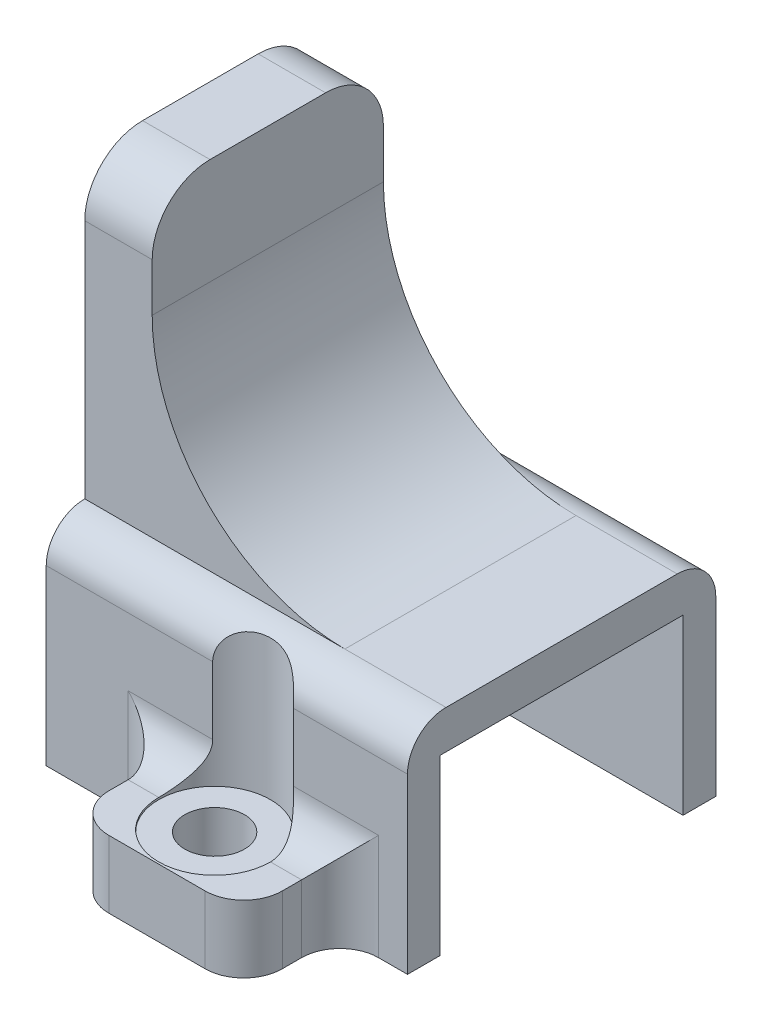
SolidWorks part; units mm, degrees
ref_plane "Alzado" through (0, 0, 0) normal (0, 0, 1) x (1, 0, 0)
ref_plane "Planta" through (0, 0, 0) normal (0, 1, 0) x (1, 0, 0)
ref_plane "Vista lateral" through (0, 0, 0) normal (1, 0, 0) x (0, 0, -1)
sketch "Croquis1" plane through (0, 0, 0) normal (0, 1, 0) x (1, 0, 0)
  line L1 (0, 0) -> (18.75, 0)
  line L2 (0, 0) -> (0, 16)
  line L3 (0, 16) -> (18.75, 16)
  line L4 (18.75, 0) -> (18.75, 16)
  dimension "D1" = 18.75
  dimension "D2" = 16
extrude "Saliente-Extruir1" add sketch "Croquis1" along normal blind 10
sketch "Croquis2" plane through (0, 0, 0) normal (0, -1, 0) x (1, 0, 0)
  line L19 (18.75, 0) -> (18.75, -16) construction
  line L20 (0, -16) -> (0, 0) construction
  line L22 (0, 0) -> (18.75, 0) construction
  line L23 (0, -1.7) -> (18.75, -1.7)
  line L24 (0, -1.7) -> (0, -14.3)
  line L25 (0, -14.3) -> (18.75, -14.3)
  line L26 (18.75, -1.7) -> (18.75, -14.3)
  line L27 (18.75, -16) -> (0, -16) construction
  point P10 (9.375, 0)
  dimension "D1" = 1.7
  dimension "D2" = 1.7
extrude "Cortar-Extruir1" cut sketch "Croquis2" against normal blind 8
sketch "Croquis3" plane through (0, 0, 0) normal (0, 0, 1) x (1, 0, 0)
  line L0 (0, 0) -> (18.75, 0) construction
  line L1 (6.25, 0) -> (15.25, 0)
  line L2 (6.25, 0) -> (6.25, 2.5)
  line L3 (6.25, 2.5) -> (15.25, 2.5)
  line L4 (15.25, 0) -> (15.25, 2.5)
  line L5 (18.75, 10) -> (18.75, 0) construction
  dimension "D1" = 2.5
  dimension "D2" = 3.5
  dimension "D3" = 9
extrude "Saliente-Extruir2" add sketch "Croquis3" along normal blind 5
sketch "Croquis4" plane through (0, 2.5, 0) normal (0, 1, 0) x (1, 0, 0)
  line L0 (18.75, 0) -> (18.75, 16) construction
  line L1 (15.25, 0) -> (6.25, 0) construction
  circle A0 centre (10.74, -2) radius 1.55
  dimension "D1" = 3.1
  dimension "D2" = 8.01
  dimension "D3" = 2
extrude "Cortar-Extruir2" cut sketch "Croquis4" against normal up to surface (2.5 mm away) up to face at (9.375, 0, -15.15)
fillet "Redondeo1" radius 2 7 edges at (9.375, 10, -16) (9.375, 10, 0) (6.25, 1.25, 5) (15.25, 1.25, 5) (10.75, 2.5, 0) (15.25, 1.25, 0) (6.25, 1.25, 0)
sketch "Croquis5" plane through (0, 10, 0) normal (0, 1, 0) x (1, 0, 0)
  circle A0 centre (10.74, -2) radius 2.9
  dimension "D1" = 5.8
extrude "Cortar-Extruir3" cut sketch "Croquis5" against normal blind 7.6
sketch "Croquis6" plane through (0, 10, 0) normal (0, 1, 0) x (1, 0, 0)
  line L0 (0, 2) -> (18.75, 2) construction
  line L1 (0, 14) -> (3.5, 14)
  line L2 (0, 14) -> (0, 2)
  line L3 (0, 2) -> (3.5, 2)
  line L4 (3.5, 14) -> (3.5, 2)
  dimension "D1" = 3.5
extrude "Saliente-Extruir3" add sketch "Croquis6" along normal blind 15.5
fillet "Redondeo2" radius 10 1 edges at (3.5, 10, -8)
fillet "Redondeo3" radius 3 2 edges at (1.75, 25.5, -14) (1.75, 25.5, -2)
sketch "Croquis7" plane through (0, 0, 0) normal (0, -1, 0) x (1, 0, 0)
  line L4 (18.75, -14.3) -> (0, -14.3)
  line L5 (0, -14.3) -> (0, -16)
  line L6 (0, -16) -> (18.75, -16)
  line L7 (18.75, -16) -> (18.75, -14.3)
  line L8 (13.25, 5) -> (8.25, 5)
  line L9 (6.25, 3) -> (6.25, 2)
  line L10 (4.25, 0) -> (0, 0)
  line L11 (0, 0) -> (0, -1.7)
  line L12 (0, -1.7) -> (18.75, -1.7)
  line L13 (18.75, -1.7) -> (18.75, 0)
  line L14 (18.75, 0) -> (17.25, 0)
  line L15 (15.25, 2) -> (15.25, 3)
  line L16 (13.25, 5) -> (8.25, 5)
  line L17 (6.25, 3) -> (6.25, 2)
  line L18 (4.25, 0) -> (0, 0)
  line L19 (0, 0) -> (0, -1.7)
  line L20 (0, -1.7) -> (18.75, -1.7)
  line L21 (18.75, -1.7) -> (18.75, 0)
  line L22 (18.75, 0) -> (17.25, 0)
  line L23 (15.25, 2) -> (15.25, 3)
  line L24 (18.75, -14.3) -> (0, -14.3)
  line L25 (0, -14.3) -> (0, -16)
  line L26 (0, -16) -> (18.75, -16)
  line L27 (18.75, -16) -> (18.75, -14.3)
  circle A0 centre (10.74, 2) radius 1.55 construction
  circle A1 centre (10.74, 2) radius 1.55
  arc A4 (8.25, 5) -> (6.25, 3) centre (8.25, 3) ccw
  arc A5 (4.25, 0) -> (6.25, 2) centre (4.25, 2) ccw
  arc A6 (15.25, 2) -> (17.25, 0) centre (17.25, 2) ccw
  arc A7 (15.25, 3) -> (13.25, 5) centre (13.25, 3) ccw
  arc A8 (8.25, 5) -> (6.25, 3) centre (8.25, 3) ccw
  arc A9 (4.25, 0) -> (6.25, 2) centre (4.25, 2) ccw
  arc A10 (15.25, 2) -> (17.25, 0) centre (17.25, 2) ccw
  arc A11 (15.25, 3) -> (13.25, 5) centre (13.25, 3) ccw
  dimension "D1" = 0
  dimension "D2" = 0
extrude "Saliente-Extruir4" add sketch "Croquis7" along normal blind 1
